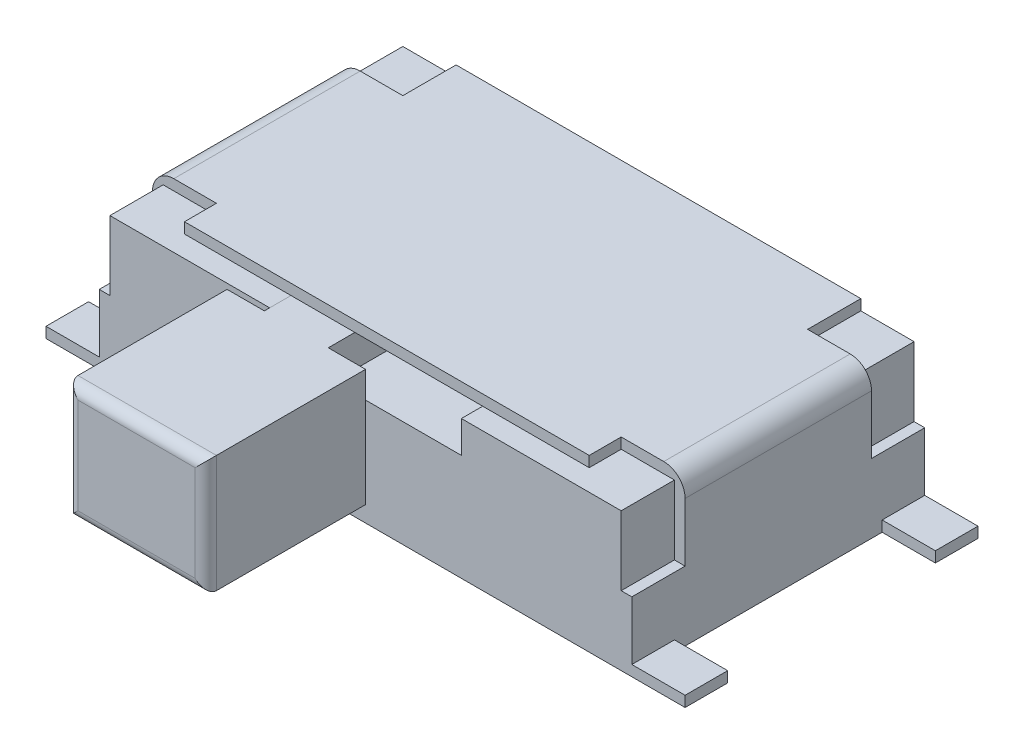
SolidWorks part; units mm, degrees
ref_plane "前视基准面" through (0, 0, 0) normal (0, 0, 1) x (1, 0, 0)
ref_plane "上视基准面" through (0, 0, 0) normal (0, 1, 0) x (1, 0, 0)
ref_plane "右视基准面" through (0, 0, 0) normal (1, 0, 0) x (0, 0, -1)
sketch "草图1" plane through (0, 0, 0) normal (0, 1, 0) x (1, 0, 0)
  line L1 (0, 0) -> (4.8, 0)
  line L2 (0, 0) -> (0, 2.75)
  line L3 (0, 2.75) -> (4.8, 2.75)
  line L4 (4.8, 0) -> (4.8, 2.75)
  dimension "D1" = 4.8
  dimension "D2" = 2.75
extrude "凸台-拉伸1" add sketch "草图1" along normal blind 1.3
sketch "草图2" plane through (0, 1.3, 0) normal (0, 1, 0) x (1, 0, 0)
  line L0 (2.4, 2.75) -> (2.4, 0) construction
  line L1 (0, 2.75) -> (4.8, 2.75) construction
  line L2 (0, 2.75) -> (0, 2.25) construction
  line L3 (0, 0) -> (4.8, 0) construction
  line L4 (4.8, 2.75) -> (4.8, 2.25) construction
  line L5 (0, 2.75) -> (0.5, 2.75) construction
  line L6 (0, 2.75) -> (0, 2.25) construction
  line L7 (0, 2.25) -> (0.5, 2.25)
  line L8 (0.5, 2.75) -> (0.5, 2.25)
  line L9 (0, 1.375) -> (5.8, 1.375) construction
  line L10 (0.5, 0) -> (0.5, 0.5)
  line L11 (0, 0.5) -> (0.5, 0.5)
  line L12 (0, 0) -> (0, 0.5) construction
  line L13 (0, 0) -> (0.5, 0) construction
  line L14 (4.8, 0) -> (4.3, 0) construction
  line L15 (4.8, 0) -> (4.8, 0.5) construction
  line L16 (4.8, 0.5) -> (4.3, 0.5)
  line L17 (4.3, 0) -> (4.3, 0.5)
  line L18 (4.3, 2.75) -> (4.3, 2.25)
  line L19 (4.8, 2.25) -> (4.3, 2.25)
  line L20 (4.8, 2.75) -> (4.8, 2.25) construction
  line L21 (4.8, 2.75) -> (4.3, 2.75) construction
  line L22 (4.8, 2.75) -> (4.8, 2.25)
  line L23 (0, 0.5) -> (-0.1, 0.5)
  line L24 (4.8, 2.25) -> (4.9, 2.25)
  line L26 (4.8, 0.5) -> (4.9, 0.5)
  line L27 (4.9, 2.25) -> (4.9, 0.5)
  line L28 (-0.1, 2.25) -> (-0.1, 0.5)
  line L29 (0, 2.25) -> (-0.1, 2.25)
  line L30 (0, 1.375) -> (0, 0.5)
  line L31 (0, 1.375) -> (0, 0) construction
  line L32 (4.8, 0.5) -> (4.8, 0) construction
  line L33 (4.8, 0.5) -> (4.8, 0)
  line L34 (0.5, 2.75) -> (4.3, 2.75)
  line L35 (4.3, 0) -> (0.5, 0)
  line M10 (0, 2.75) -> (0, 0)
  line M11 (0, 0) -> (4.8, 0)
  line M12 (4.8, 0) -> (4.8, 2.75)
  line M13 (4.8, 2.75) -> (0, 2.75)
  dimension "D1" = 0.5
  dimension "D2" = 0.1
extrude "凸台-拉伸3" add sketch "草图2" along normal blind 0.1 separate body contours L19 L18 L8 L7 L11 L10 L17 L16 M12 M13 M10 M11 | L29 L28 L23 M10 | L27 L24 L26 M12 region at (-0.05, 1.3, -1.375) region at (2.4, 1.3, -1.375) region at (4.85, 1.3, -1.375)
sketch "草图3" plane through (0, 0, 0) normal (-1, 0, 0) x (0, 0, 1)
  line L0 (-2.75, 1.3) -> (0, 1.3) construction
  line L1 (-2.25, 1.4) -> (-2.25, 1.3) construction
  line L2 (-0.5, 1.4) -> (-0.5, 1.3) construction
  line L3 (0, 1.3) -> (0, 0) construction
  line L4 (-2.75, 0) -> (0, 0)
  line L5 (-2.75, 0) -> (-2.75, 0.65)
  line L6 (-2.75, 0.65) -> (0, 0.65) construction
  line L7 (0, 0) -> (0, 0.65)
  line L8 (-2.75, 0.65) -> (-2.25, 0.65)
  line L9 (-2.25, 1.3) -> (-0.5, 1.3)
  line L10 (-2.25, 1.3) -> (-2.25, 0.65)
  line L11 (-2.25, 0.65) -> (-0.5, 0.65) construction
  line L12 (-0.5, 1.3) -> (-0.5, 0.65)
  line L13 (-0.5, 0.65) -> (0, 0.65)
  point P0 (-2.25, 1.3)
  point P1 (-0.5, 1.3)
  dimension "D1" = 0.65
extrude "凸台-拉伸4" add sketch "草图3" along normal blind 0.1
ref_plane "中心" through (2.4, 0, 0) normal (1, 0, 0) x (0, 0, -1)
mirror "镜向16" about plane through (2.4, 0, 0) normal (1, 0, 0) of bodies 109
sketch "草图4" plane through (-0.1, 0, 0) normal (-1, 0, 0) x (0, 0, 1)
  line L0 (-1.375, 1.3) -> (-1.375, 0) construction
  line L1 (-2.75, 0) -> (-2.35, 0)
  line L2 (-2.75, 0) -> (-2.75, 0.1)
  line L3 (-2.75, 0.1) -> (-2.35, 0.1)
  line L4 (-2.35, 0) -> (-2.35, 0.1)
  line L5 (-2.25, 1.3) -> (-0.5, 1.3) construction
  line L6 (-2.75, 0) -> (0, 0) construction
  line L7 (-0.4, 0) -> (-0.4, 0.1)
  line L8 (0, 0.1) -> (-0.4, 0.1)
  line L9 (0, 0) -> (0, 0.1)
  line L10 (0, 0) -> (-0.4, 0)
  dimension "D1" = 0.4
  dimension "D2" = 0.1
extrude "凸台-拉伸5" add sketch "草图4" along normal blind 0.5
mirror "镜向17" about plane through (2.4, 0, 0) normal (1, 0, 0) of bodies 111
sketch "草图5" plane through (0, 1.4, 0) normal (0, 1, 0) x (1, 0, 0)
  line L0 (4.3, 0) -> (4.3, 0.5) construction
  line L1 (0.5, 0) -> (4.3, 0)
  line L2 (0.5, 0) -> (0.5, 0.2)
  line L3 (0.5, 0.2) -> (4.3, 0.2)
  line L4 (4.3, 0) -> (4.3, 0.2)
  dimension "D1" = 0.2
extrude "切除-拉伸1" cut sketch "草图5" against normal blind 0.1
sketch "草图6" plane through (0, 0, 0) normal (0, 0, 1) x (1, 0, 0)
  line L0 (0, 1.3) -> (4.8, 1.3) construction
  line L1 (1.5, 1.3) -> (3.3, 1.3)
  line L2 (1.5, 1.3) -> (1.5, 1)
  line L3 (1.5, 1) -> (3.3, 1)
  line L4 (3.3, 1.3) -> (3.3, 1)
  line L5 (1.5, 1.3) -> (3.3, 1) construction
  line L6 (1.5, 1) -> (3.3, 1.3) construction
  line L7 (2.4, 0) -> (2.4, 1.3) construction
  line L8 (-0.6, 0) -> (5.4, 0) construction
  point P0 (2.4, 1.15)
  point P11 (0, 0)
  dimension "D1" = 0.3
  dimension "D2" = 1.8
extrude "切除-拉伸2" cut sketch "草图6" against normal blind 1
sketch "草图7" plane through (0, 0, -1) normal (0, 0, 1) x (1, 0, 0)
  line L0 (3.3, 1.3) -> (1.5, 1.3) construction
  line L1 (1.5, 1) -> (2.1, 1)
  line L2 (1.5, 1) -> (1.5, 1.3)
  line L3 (1.5, 1.3) -> (2.1, 1.3)
  line L4 (2.1, 1) -> (2.1, 1.3)
  dimension "D1" = 0.6
extrude "凸台-拉伸6" add sketch "草图7" along normal blind 1.05 separate body
sketch "草图8" plane through (0, 0, 0.05) normal (0, 0, 1) x (1, 0, 0)
  line L0 (2.1, 1.3) -> (1.5, 1.3) construction
  line L1 (1.15, 1.3) -> (2.45, 1.3)
  line L2 (1.15, 1.3) -> (1.15, 0.2)
  line L3 (1.15, 0.2) -> (2.45, 0.2)
  line L4 (2.45, 1.3) -> (2.45, 0.2)
  line L5 (1.8, 1.3) -> (1.8, 1) construction
  line L6 (1.5, 1) -> (2.1, 1) construction
  line L7 (1.8, 0.2) -> (1.8, 1.3) construction
  point P4 (1.8, 1.3)
  dimension "D1" = 1.1
  dimension "D2" = 1.3
extrude "凸台-拉伸7" add sketch "草图8" along normal blind 1.5
sketch "草图9" plane through (0, 0, -2.75) normal (0, 0, -1) x (-1, 0, 0)
  line L0 (-2.4, 1.4) -> (-2.4, 0) construction
  line L1 (-4.3, 1.4) -> (-0.5, 1.4) construction
  line L2 (-5.4, 0) -> (0.6, 0) construction
  line L3 (-1.6, 0.15) -> (-1.2, 0.15)
  line L4 (-2.6, 0.15) -> (-2.2, 0.15)
  line L5 (-2.6, 0.15) -> (-2.6, 0)
  line L6 (-2.6, 0) -> (-2.2, 0)
  line L7 (-2.2, 0.15) -> (-2.2, 0)
  line L8 (-2.6, 0.15) -> (-2.2, 0) construction
  line L9 (-2.6, 0) -> (-2.2, 0.15) construction
  line L10 (-1.6, 0.15) -> (-1.6, 0)
  line L11 (-1.6, 0) -> (-1.2, 0)
  line L12 (-1.2, 0.15) -> (-1.2, 0)
  line L13 (-1.4, 1.4) -> (-1.4, 0) construction
  line L14 (-1.6, 0.15) -> (-1.2, 0) construction
  line L15 (-1.6, 0) -> (-1.2, 0.15) construction
  line L16 (-3.6, 0.15) -> (-3.2, 0.15)
  line L17 (-3.6, 0.15) -> (-3.6, 0)
  line L18 (-3.6, 0) -> (-3.2, 0)
  line L19 (-3.2, 0.15) -> (-3.2, 0)
  line L20 (-3.4, 1.4) -> (-3.4, 0) construction
  line L21 (-3.6, 0.15) -> (-3.2, 0) construction
  line L22 (-3.6, 0) -> (-3.2, 0.15) construction
  point P6 (-2.4, 0.075)
  point P14 (-1.4, 0.075)
  point P21 (-3.4, 0.075)
  dimension "D1" = 0.15
  dimension "D2" = 0.4
  dimension "D3" = 2
  dimension "D4" = 2
extrude "凸台-拉伸8" add sketch "草图9" along normal blind 0.9
fillet "圆角1" radius 0.2 2 edges at (4.9, 1.4, -1.375) (-0.1, 1.4, -1.375)
fillet "圆角2" radius 0.1 4 edges at (1.8, 1.3, 1.55) (2.45, 0.75, 1.55) (1.8, 0.2, 1.55) (1.15, 0.75, 1.55)
sketch "草图10" plane through (0, 0, 0) normal (0, -1, 0) x (1, 0, 0)
  line L0 (-0.1, -1.375) -> (4.9, -1.375) construction
  line L1 (-0.1, -2.35) -> (-0.1, -0.4) construction
  line L2 (4.9, -2.35) -> (4.9, -0.4) construction
  line L3 (2.4, -0.77) -> (2.4, 0.77) construction
  circle A0 centre (0.9, -1.375) radius 0.3815
  circle A1 centre (3.9, -1.375) radius 0.3815
  point P8 (0, 0)
  dimension "D1" = 0.763
  dimension "D2" = 1.5
extrude "凸台-拉伸9" add sketch "草图10" along normal blind 0.5
fillet "圆角3" radius 0.2 2 edges at (3.9, -0.5, -0.9935) (0.9, -0.5, -1.7565)
